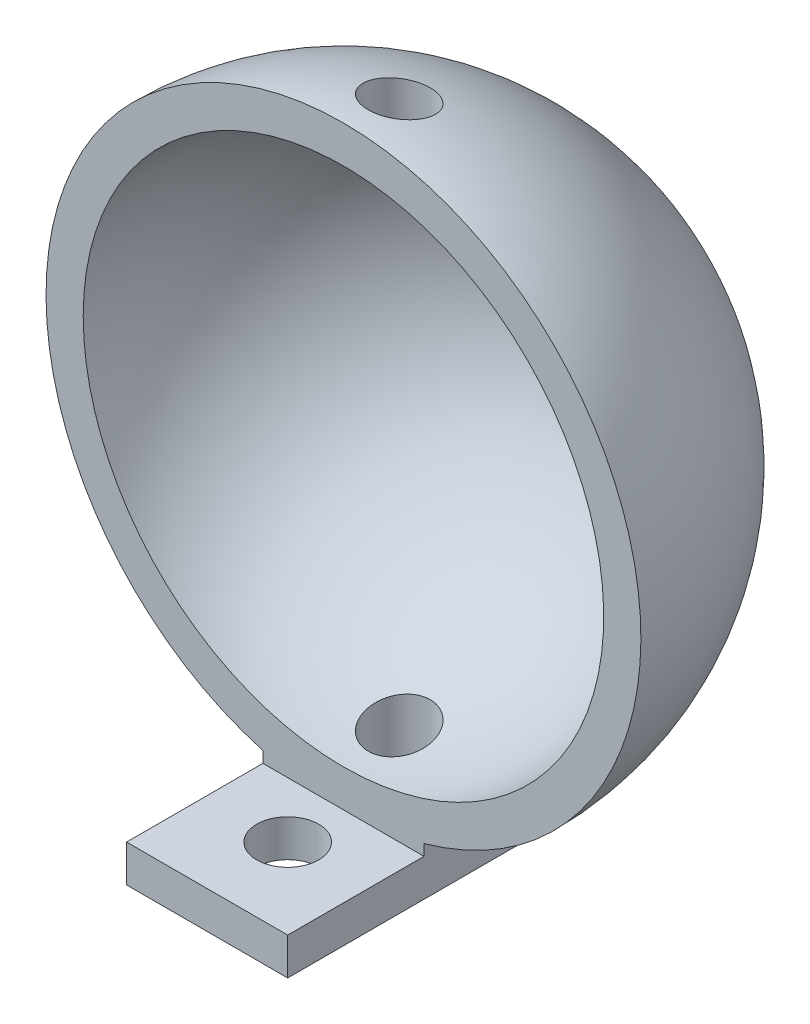
SolidWorks part; units mm, degrees
ref_plane "Front Plane" through (0, 0, 0) normal (0, 0, 1) x (1, 0, 0)
ref_plane "Top Plane" through (0, 0, 0) normal (0, 1, 0) x (1, 0, 0)
ref_plane "Right Plane" through (0, 0, 0) normal (1, 0, 0) x (0, 0, -1)
sketch "Sketch4" plane through (0, 60.25, 0) normal (0, 1, 0) x (1, 0, 0)
  line L0 (-103.35, -1.5487) -> (10.75, -1.5487) construction
  line L1 (-5.25, 13.9513) -> (1.25, 13.9513)
  line L2 (-5.25, 13.9513) -> (-5.25, 2.9513)
  line L3 (-5.25, 2.9513) -> (1.25, 2.9513)
  line L4 (1.25, 13.9513) -> (1.25, 2.9513)
  line L5 (1.25, 6) -> (1.25, 1.5) construction
  line L6 (-3.25, 6.2013) -> (-5.25, 6.2013) construction
  line L7 (-2, 4.9513) -> (-2, 2.9513) construction
  line L9 (-0.75, 6.2013) -> (1.25, 6.2013) construction
  line L10 (-2, 7.4513) -> (-2, 9.4513) construction
  line L11 (-2, 11.9513) -> (-2, 13.9513) construction
  line L12 (-38.5, -1.5487) -> (38.5, -1.5487) construction
  line L13 (-5.25, 8.4513) -> (1.25, 8.4513)
  circle A0 centre (-2, 6.2013) radius 1.25
  circle A2 centre (-2, 8.4513) radius 10 construction
  circle A4 centre (-2, 10.7013) radius 1.25
  point P15 (-2, 8.4513)
  dimension "D1" = 20
  dimension "D2" = 2.5
  dimension "D3" = 2
  dimension "D4" = 2
extrude "Boss-Extrude2" add sketch "Sketch4" along normal blind 1.5 contours A0 | A4 | L2 L3 L4 L1 region at (-2, 60.25, -6.2013) region at (-2, 60.25, -10.7013)
ref_plane "Plane3" through (-2, 0, 0) normal (-1, 0, 0) x (0, 0, 1)
sketch "Sketch5" plane through (-2, 0, 0) normal (-1, 0, 0) x (0, 0, 1)
  line L0 (-8.4513, 61.75) -> (-8.4513, 63.25)
  line L4 (-18.9513, 73.75) -> (-8.4513, 73.75) construction
  line L5 (-18.9513, 73.75) -> (-20.4513, 73.75)
  line L6 (-13.9513, 61.75) -> (-2.9513, 61.75) construction
  line L7 (-13.9513, 61.75) -> (-2.9513, 61.75) construction
  arc A0 (-20.4513, 73.75) -> (-8.4513, 61.75) centre (-8.4513, 73.75) ccw
  arc A1 (-18.9513, 73.75) -> (-8.4513, 63.25) centre (-8.4513, 73.75) ccw
  point P3 (0, 0)
  point P4 (0, 0)
  point P5 (0, 0)
  point P6 (0, 0)
  point P7 (0, 0)
  point P9 (0, 0)
  point P12 (-8.3411, 61.7505)
  point P15 (0, 0)
  point P16 (-8.4513, 61.75)
  point P17 (0, 0)
  dimension "D1" = 21
  dimension "D2" = 1.5
revolve "Revolve5" add sketch "Sketch5" angle 360 about L4
extrude "Boss-Extrude3" add sketch "Sketch4<5>" along normal up to surface (5.1671 mm away) contours L2 L13 L4 L1 A4 region at (-2, 60.25, -13.8661) up to face at (-12.5, 73.75, -8.4513)
sketch "Sketch4<5>" plane through (0, 60.25, 0) normal (0, 1, 0) x (1, 0, 0) same geometry as "Sketch4"
extrude "Cut-Extrude1" cut sketch "Sketch4<6>" along normal through all contours A4
sketch "Sketch4<6>" plane through (0, 60.25, 0) normal (0, 1, 0) x (1, 0, 0) same geometry as "Sketch4"
equation "\"D2@Sketch4\"=3-.5"
equation "\"D1@Sketch5\"=20+1"
